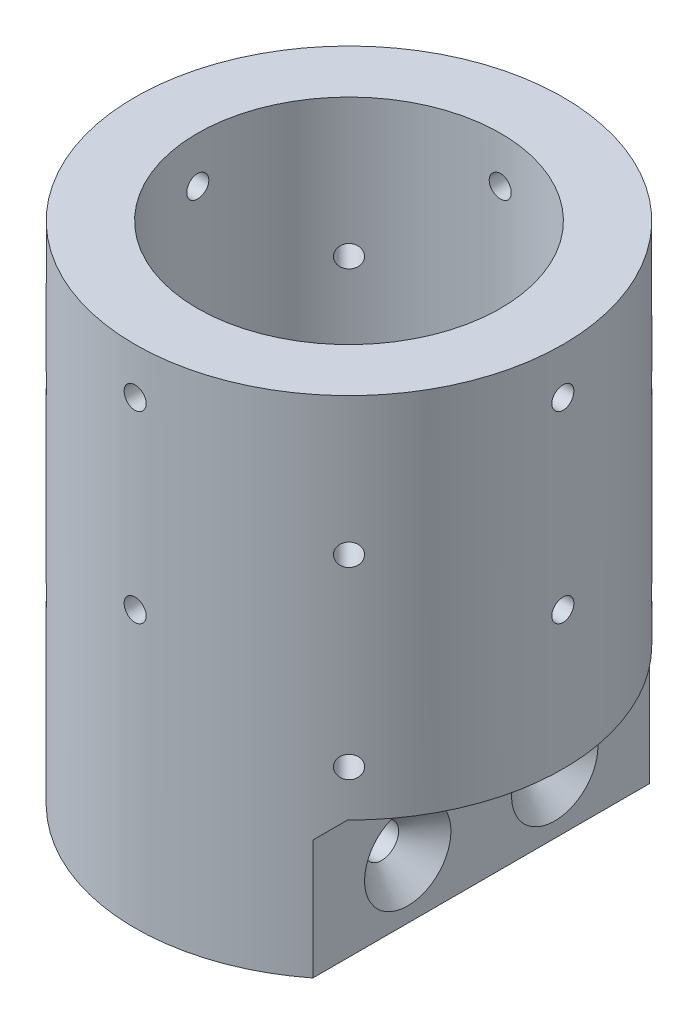
SolidWorks part; units mm, degrees
ref_plane "Спереди" through (0, 0, 0) normal (0, 0, 1) x (1, 0, 0)
ref_plane "Сверху" through (0, 0, 0) normal (0, 1, 0) x (1, 0, 0)
ref_plane "Справа" through (0, 0, 0) normal (1, 0, 0) x (0, 0, -1)
sketch "Эскиз1" plane through (0, 0, 0) normal (0, 1, 0) x (1, 0, 0)
  circle A0 centre (0, 0) radius 23.3
  dimension "D1" = 46.6
extrude "Бобышка-Вытянуть1" add sketch "Эскиз1" along normal blind 5
sketch "Эскиз2" plane through (0, 5, 0) normal (0, 1, 0) x (1, 0, 0)
  circle A0 centre (0, 0) radius 23.3
  circle A1 centre (0, 0) radius 16.5
  circle A2 centre (0, 0) radius 23.3 construction
  dimension "D1" = 33
  dimension "D2" = 0
extrude "Бобышка-Вытянуть2" add sketch "Эскиз2" along normal blind 35
chamfer "Фаска8" distance 2 angle 45 1 edges at (0, 5, 16.5)
sketch "Эскиз3" plane through (0, 0, 0) normal (1, 0, 0) x (0, 0, -1)
  line L0 (-23.3, 20) -> (28.0263, 20) construction
  line L1 (-23.3, 40) -> (-23.3, 0) construction
  line L2 (16.5, 40) -> (-16.5, 40) construction
  circle A1 centre (0, 35) radius 1.2
  dimension "D1" = 2.4
  dimension "D2" = 5
extrude "Вырез-Вытянуть1" cut sketch "Эскиз3" against normal through all
ref_plane "Плоскость1" through (0, 0, 0) normal (0.7071, 0, 0.7071) x (0, -1, 0)
sketch "Эскиз4" plane through (0, 0, 0) normal (0.7071, 0, 0.7071) x (0, -1, 0)
  line L0 (-20, 23.3) -> (-20, -30.0625) construction
  line L1 (0, 23.3) -> (-40, 23.3) construction
  line L3 (0, -23.3) -> (0, 23.3) construction
  circle A1 centre (-5, 0) radius 1.2
  dimension "D1" = 5
  dimension "D2" = 2.4
extrude "Вырез-Вытянуть2" cut sketch "Эскиз4" against normal through all from offset 16.3 offset against normal yes
pattern_circular "Круговой массив1" count 4 over 360 about axis through (0, 5, 0) along (0, -1, 0) of "Вырез-Вытянуть2"
pattern_circular "Круговой массив2" count 4 over 360 about axis through (0, 5, 0) along (0, -1, 0) of "Вырез-Вытянуть1"
pattern_linear "Линейный массив3" count 2 spacing 20 along (0, 1, 0) of "Круговой массив1"
pattern_linear "Линейный массив4" count 2 spacing 20 along (0, -1, 0) of "Круговой массив2"
sketch "Эскиз12" plane through (0, 0, 0) normal (0, -1, 0) x (1, 0, 0)
  line L1 (14.3923, 18.3235) -> (14.3923, -18.3235)
  line L20 (0, 15) -> (-2.7835, 17.7835)
  line L21 (-2.7835, -17.7835) -> (0, -15)
  line L22 (0, -15) -> (0, 15)
  line L23 (0, 15) -> (-2.7835, 17.7835)
  line L24 (-2.7835, -17.7835) -> (0, -15)
  line L25 (0, -15) -> (0, 15)
  circle A6 centre (0, 0) radius 23.3 construction
  arc A7 (14.3923, 18.3235) -> (14.3923, -18.3235) centre (0, 0) ccw
  arc A13 (-2.7835, 17.7835) -> (-2.7835, -17.7835) centre (0, 0) ccw
  arc A14 (-2.7835, 17.7835) -> (-2.7835, -17.7835) centre (0, 0) ccw
  dimension "D1" = 0
extrude "Бобышка-Вытянуть3" add sketch "Эскиз12" along normal blind 15 contours L1 region at (13.7929, 0, 0)
sketch "Эскиз13" plane through (0, -15, 0) normal (0, -1, 0) x (1, 0, 0)
  line L14 (-2.6786, -18.1029) -> (0.3, -15.1243)
  line L15 (0.3, 15.1243) -> (-2.6786, 18.1029)
  line L16 (0.3, -15.1243) -> (0.3, 15.1243)
  line L17 (-2.6786, -18.1029) -> (0.3, -15.1243)
  line L18 (0.3, 15.1243) -> (-2.6786, 18.1029)
  line L19 (0.3, -15.1243) -> (0.3, 15.1243)
  arc A5 (-2.6786, 18.1029) -> (-2.6786, -18.1029) centre (0, 0) ccw
  arc A6 (-2.6786, 18.1029) -> (-2.6786, -18.1029) centre (0, 0) ccw
  dimension "D1" = 0.3
extrude "Вырез-Вытянуть10" cut sketch "Эскиз13" against normal up to surface (15 mm away) up to face at (18.8461, 0, 0)
chamfer "Фаска4" distance 2 angle 45 1 edges at (14.3923, 0, 0)
chamfer "Фаска6" distance 2 angle 45 4 edges at (-1.1893, 0, -16.6136) (-18.3, 0, 0) (0.3, 0, 0) (-1.1893, 0, 16.6136)
chamfer "Фаска7" distance 2 angle 45 4 edges at (-1.1893, -15, -16.6136) (-18.3, -15, 0) (-1.1893, -15, 16.6136) (0.3, -15, 0)
hole_wizard "Зенковка для винта с полупотайной головкой M41" positions "Эскиз14" profile "Эскиз15" countersink size "M4" standard "ISO" end condition through all
sketch "Эскиз14" plane through (14.3923, -676.2045, -24.0267) normal (1, 0, 0) x (0, 0.0202, -0.9998)
  line L0 (-10.4265, 674.5519) -> (-10.6887, 661.5545) construction
  line L4 (-10.5576, 668.0532) -> (-20.4413, 668.0532) construction
  line L5 (-20.4413, 668.0532) -> (-1.8045, 668.0532) construction
  point P0 (-18.5576, 668.0532)
  point P19 (-2.5641, 667.7306)
sketch "Эскиз15" plane through (14.3923, -8.6613, 7.9984) normal (0, 1, 0) x (0, 0, -1)
  line L0 (0, 0) -> (0, 37.6923)
  line L1 (0, 37.6923) -> (1.85, 37.6923)
  line L2 (1.85, 37.6923) -> (1.85, 2.85)
  line L3 (1.85, 2.85) -> (4.7, 0)
  line L4 (4.7, 0) -> (0, 0)
  line L5 (-1.85, 2.85) -> (-4.7, 0) construction
  line L6 (0, -6.35) -> (0, 107.95) construction
  dimension "Диаметр сквозного отверстия" = 3.7
  dimension "Глубина сквозного отверстия" = 37.6923
  dimension "Диаметр передней зенковки" = 9.4
  dimension "Угол передней зенковки" = 90
sketch "Эскиз17" plane through (0, -15, 0) normal (0, -1, 0) x (1, 0, 0)
  circle A0 centre (5.3288, 0) radius 2.5
extrude "Вырез-Вытянуть11" cut sketch "Эскиз17" against normal blind 86
